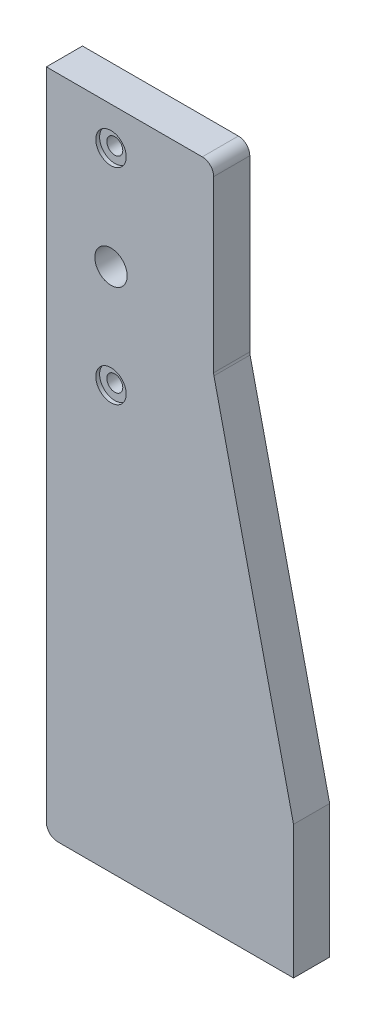
SolidWorks part; units mm, degrees
ref_plane "前视基准面" through (0, 0, 0) normal (0, 0, 1) x (1, 0, 0)
ref_plane "上视基准面" through (0, 0, 0) normal (0, 1, 0) x (1, 0, 0)
ref_plane "右视基准面" through (0, 0, 0) normal (1, 0, 0) x (0, 0, -1)
sketch "草图5" plane through (0, 0, 0) normal (0, 0, 1) x (1, 0, 0)
  line L0 (0, 0) -> (0, 175)
  line L1 (0, 175) -> (44, 175)
  line L2 (44, 175) -> (44, 127)
  line L3 (44, 127) -> (65, 35)
  line L4 (65, 35) -> (65, 0)
  line L5 (65, 0) -> (0, 0)
  line L6 (16, 175) -> (16, 0) construction
  dimension "D1" = 65
  dimension "D2" = 175
  dimension "D3" = 44
  dimension "D4" = 48
  dimension "D5" = 35
  dimension "D6" = 16
extrude "凸台-拉伸1" add sketch "草图5" along normal blind 9.5
sketch "草图6" plane through (0, 0, 9.5) normal (0, 0, 1) x (1, 0, 0)
  line L0 (17, 175) -> (17, 0) construction
  line L1 (44, 175) -> (0, 175) construction
  line L2 (0, 0) -> (65, 0) construction
  line L3 (0, 175) -> (0, 0) construction
  circle A0 centre (17, 165) radius 2.1
  circle A1 centre (17, 111) radius 2.1
  dimension "D2" = 4.2
  dimension "D3" = 10
  dimension "D4" = 54
  dimension "D1" = 17
extrude "切除-拉伸5" cut sketch "草图6" against normal through all contours A1 | A0
sketch "草图7" plane through (0, 0, 9.5) normal (0, 0, 1) x (1, 0, 0)
  circle A0 centre (17, 165) radius 4
  circle A1 centre (17, 111) radius 4
  dimension "D1" = 8
extrude "切除-拉伸6" cut sketch "草图7" against normal blind 1
fillet "圆角1" radius 3 3 edges at (0, 0, 4.75) (44, 127, 4.75) (44, 175, 4.75)
sketch "草图8" plane through (0, 0, 9.5) normal (0, 0, 1) x (1, 0, 0)
  line L0 (17, 165) -> (17, 111) construction
  circle A3 centre (17, 138) radius 4.25
  dimension "D1" = 8.5
extrude "切除-拉伸7" cut sketch "草图8" against normal blind 10
